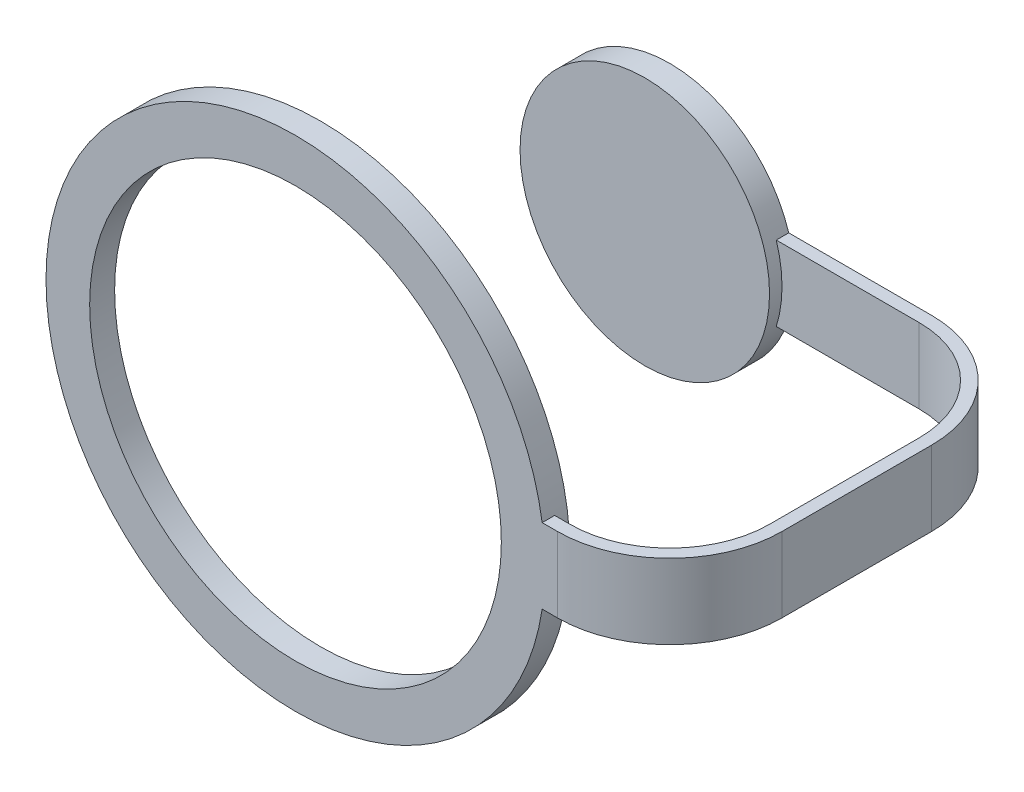
SolidWorks part; units mm, degrees
ref_plane "Front Plane" through (0, 0, 0) normal (0, 0, 1) x (1, 0, 0)
ref_plane "Top Plane" through (0, 0, 0) normal (0, 1, 0) x (1, 0, 0)
ref_plane "Right Plane" through (0, 0, 0) normal (1, 0, 0) x (0, 0, -1)
ref_plane "Plane2" through (0, 0, 13) normal (0, 0, 1) x (1, 0, 0)
sketch "Sketch7" plane through (0, 0, 13) normal (0, 0, 1) x (1, 0, 0)
  circle A0 centre (0, 0) radius 10
  circle A1 centre (0, 0) radius 8.25
  dimension "D1" = 16.5
  dimension "D2" = 20
extrude "Boss-Extrude3" add sketch "Sketch7" along normal blind 1 separate body
sketch "Sketch8" plane through (0, 0, 0) normal (0, 0, 1) x (1, 0, 0)
  circle A0 centre (0, 0) radius 5
  dimension "D1" = 10
extrude "Boss-Extrude4" add sketch "Sketch8" against normal blind 1
sketch "Sketch9" plane through (0, 0, 0) normal (0, 1, 0) x (1, 0, 0)
  line L0 (10, -13.5) -> (10.5, -13.5)
  line L1 (10, -14) -> (10, -13) construction
  line L2 (14.5, -9.5) -> (14.5, -3.5)
  line L3 (10.5, 0.5) -> (5, 0.5)
  line L4 (5, 0) -> (5, 1) construction
  line L5 (10.5, 1) -> (5, 1)
  line L6 (15, -9.5) -> (15, -3.5)
  line L7 (10, -14) -> (10.5, -14)
  line L8 (10, -14) -> (9.7, -14)
  line L9 (-10, -14) -> (10, -14) construction
  line L10 (9.7, -14) -> (9.7, -13.5)
  line L11 (9.7, -13.5) -> (10, -13.5)
  line L12 (5, 0.5) -> (4.7, 0.5)
  line L13 (4.7, 0.5) -> (4.7, 1)
  line L14 (4.7, 1) -> (5, 1)
  arc A0 (10.5, 0.5) -> (14.5, -3.5) centre (10.5, -3.5) cw
  arc A1 (14.5, -9.5) -> (10.5, -13.5) centre (10.5, -9.5) cw
  arc A2 (10.5, 1) -> (15, -3.5) centre (10.5, -3.5) cw
  arc A3 (15, -9.5) -> (10.5, -14) centre (10.5, -9.5) cw
  dimension "D1" = 4
  dimension "D2" = 4.5
  dimension "D4" = 0.3
  dimension "D5" = 0.3
  dimension "D3" = 0.5
extrude "Boss-Extrude5" add sketch "Sketch9" along normal blind 1.5 and the other way blind 1.5
